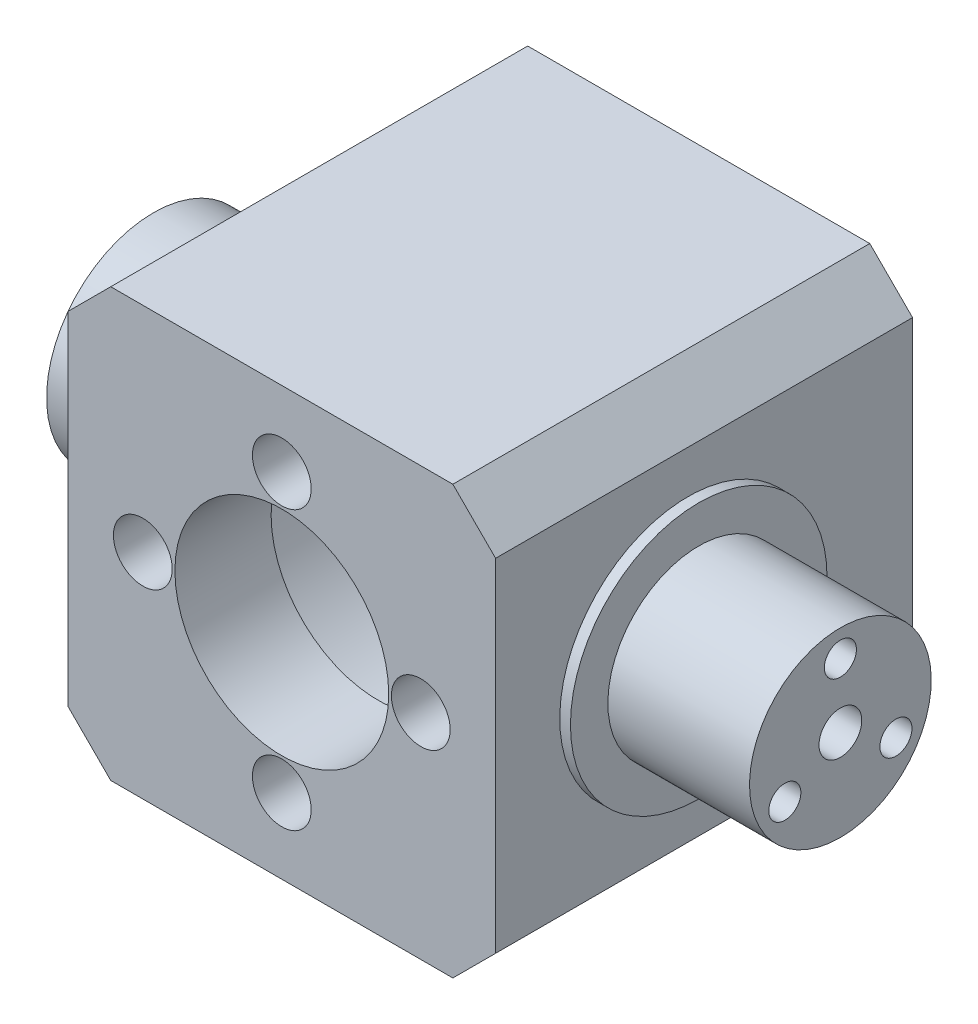
SolidWorks part; units mm, degrees
material "ABS"
ref_plane "Plan de face" through (0, 0, 0) normal (0, 0, 1) x (1, 0, 0)
ref_plane "Plan de dessus" through (0, 0, 0) normal (0, 1, 0) x (1, 0, 0)
ref_plane "Plan de droite" through (0, 0, 0) normal (1, 0, 0) x (0, 0, -1)
sketch "Esquisse1" plane through (0, 0, 0) normal (0, 0, 1) x (1, 0, 0)
  line L1 (20, 20) -> (-20, 20)
  line L2 (20, 20) -> (20, -20)
  line L3 (20, -20) -> (-20, -20)
  line L4 (-20, 20) -> (-20, -20)
  line L5 (20, 20) -> (-20, -20) construction
  line L6 (20, -20) -> (-20, 20) construction
  circle A0 centre (0, 0) radius 16
  dimension "D1" = 32
  dimension "D2" = 40
extrude "Boss.-Extru.1" add sketch "Esquisse1" along normal blind 30
sketch "Esquisse2" plane through (0, 0, 30) normal (0, 0, 1) x (1, 0, 0)
  line L4 (-20, 20) -> (-20, -20)
  line L5 (-20, -20) -> (20, -20)
  line L6 (20, -20) -> (20, 20)
  line L7 (20, 20) -> (-20, 20)
  line L8 (-20, 20) -> (-20, -20)
  line L9 (-20, -20) -> (20, -20)
  line L10 (20, -20) -> (20, 20)
  line L11 (20, 20) -> (-20, 20)
  dimension "D1" = 0
extrude "Boss.-Extru.2" add sketch "Esquisse2" along normal blind 5
sketch "Esquisse3" plane through (0, 0, 35) normal (0, 0, 1) x (1, 0, 0)
  circle A0 centre (0, 0) radius 13 construction
  circle A1 centre (0, 13) radius 1.5
  circle A2 centre (13, 0) radius 1.5
  circle A3 centre (0, -13) radius 1.5
  circle A4 centre (-13, 0) radius 1.5
  dimension "D1" = 26
  dimension "D2" = 3
  dimension "D3" = 4
extrude "Enlèv. mat.-Extru.1" cut sketch "Esquisse3" against normal blind 5
sketch "Esquisse4" plane through (0, 0, 35) normal (0, 0, 1) x (1, 0, 0)
  circle A0 centre (0, 0) radius 10
  dimension "D1" = 20
extrude "Enlèv. mat.-Extru.2" cut sketch "Esquisse4" against normal blind 5
sketch "Esquisse5" plane through (-20, 0, 0) normal (-1, 0, 0) x (0, 0, 1)
  line L0 (35, 20) -> (35, -20) construction
  circle A0 centre (21, 0) radius 10
  dimension "D1" = 20
  dimension "D2" = 14
extrude "Boss.-Extru.3" add sketch "Esquisse5" along normal blind 10
sketch "Esquisse6" plane through (-20, 0, 0) normal (-1, 0, 0) x (0, 0, 1)
  circle A2 centre (21, 0) radius 12
  circle A3 centre (21, 0) radius 12
  dimension "D1" = 2
extrude "Boss.-Extru.4" add sketch "Esquisse6" along normal blind 1
sketch "Esquisse7" plane through (20, 0, 0) normal (1, 0, 0) x (0, 0, -1)
  line L0 (-35, -20) -> (-35, 20) construction
  circle A0 centre (-21, 0) radius 8.5
  dimension "D1" = 17
  dimension "D2" = 14
extrude "Boss.-Extru.5" add sketch "Esquisse7" along normal blind 14.25
sketch "Esquisse8" plane through (20, 0, 0) normal (1, 0, 0) x (0, 0, -1)
  circle A0 centre (-21, 0) radius 12
  dimension "D1" = 24
extrude "Boss.-Extru.6" add sketch "Esquisse8" along normal blind 1
sketch "Esquisse9" plane through (0, 0, 35) normal (0, 0, 1) x (1, 0, 0)
  line L6 (20, 20) -> (-20, 20)
  line L7 (-20, 20) -> (-20, -20)
  line L9 (-20, -20) -> (20, -20)
  line L10 (20, -20) -> (20, 20)
  line L12 (20, 20) -> (-20, 20)
  line L13 (-20, 20) -> (-20, -20)
  line L15 (-20, -20) -> (20, -20)
  line L16 (20, -20) -> (20, 20)
  circle A9 centre (0, 13) radius 2.75
  circle A10 centre (-13, 0) radius 2.75
  circle A11 centre (0, -13) radius 2.75
  circle A12 centre (13, 0) radius 2.75
  circle A13 centre (0, 0) radius 10
  circle A14 centre (0, 0) radius 10 construction
  dimension "D2" = 5.5
  dimension "D1" = 0
extrude "Boss.-Extru.7" add sketch "Esquisse9" along normal blind 4
sketch "Esquisse10" plane through (34.25, 0, 0) normal (1, 0, 0) x (0, 0, -1)
  circle A0 centre (-21, 0) radius 6 construction
  circle A1 centre (-21, 6) radius 1.5
  circle A2 centre (-15.8038, -3) radius 1.5
  circle A3 centre (-21, 0) radius 6 construction
  circle A4 centre (-26.1962, -3) radius 1.5
  circle A5 centre (-21, 0) radius 6 construction
  circle A6 centre (-21, 0) radius 2
  dimension "D1" = 3
  dimension "D3" = 12
  dimension "D4" = 4
  dimension "D2" = 3
extrude "Enlèv. mat.-Extru.3" cut sketch "Esquisse10" against normal through all
chamfer "Chanfrein1" distance 4 angle 45 4 edges at (-20, -20, 19.5) (20, -20, 19.5) (20, 20, 19.5) (-20, 20, 19.5)
sketch "Esquisse11" plane through (0, 0, 0) normal (1, 0, 0) x (0, 0, -1)
  circle A0 centre (-15.8038, -3) radius 1.5 construction
  circle A1 centre (-26.1962, -3) radius 1.5 construction
  circle A2 centre (-21, 0) radius 2 construction
  circle A3 centre (-21, 6) radius 1.5 construction
  circle A4 centre (-15.8038, -3) radius 1.5 construction
  circle A5 centre (-26.1962, -3) radius 1.5 construction
  circle A6 centre (-21, 0) radius 2 construction
  circle A7 centre (-21, 6) radius 1.5 construction
  circle A8 centre (-21, 6) radius 2.1
  circle A9 centre (-26.1962, -3) radius 2.1
  circle A10 centre (-15.8038, -3) radius 2.1
  circle A11 centre (-21, 0) radius 2.6
  dimension "D1" = 4.2
  dimension "D2" = 5.2
extrude "Enlèv. mat.-Extru.4" [suppressed] cut sketch "Esquisse11" against normal blind 22 and the other way blind 22
